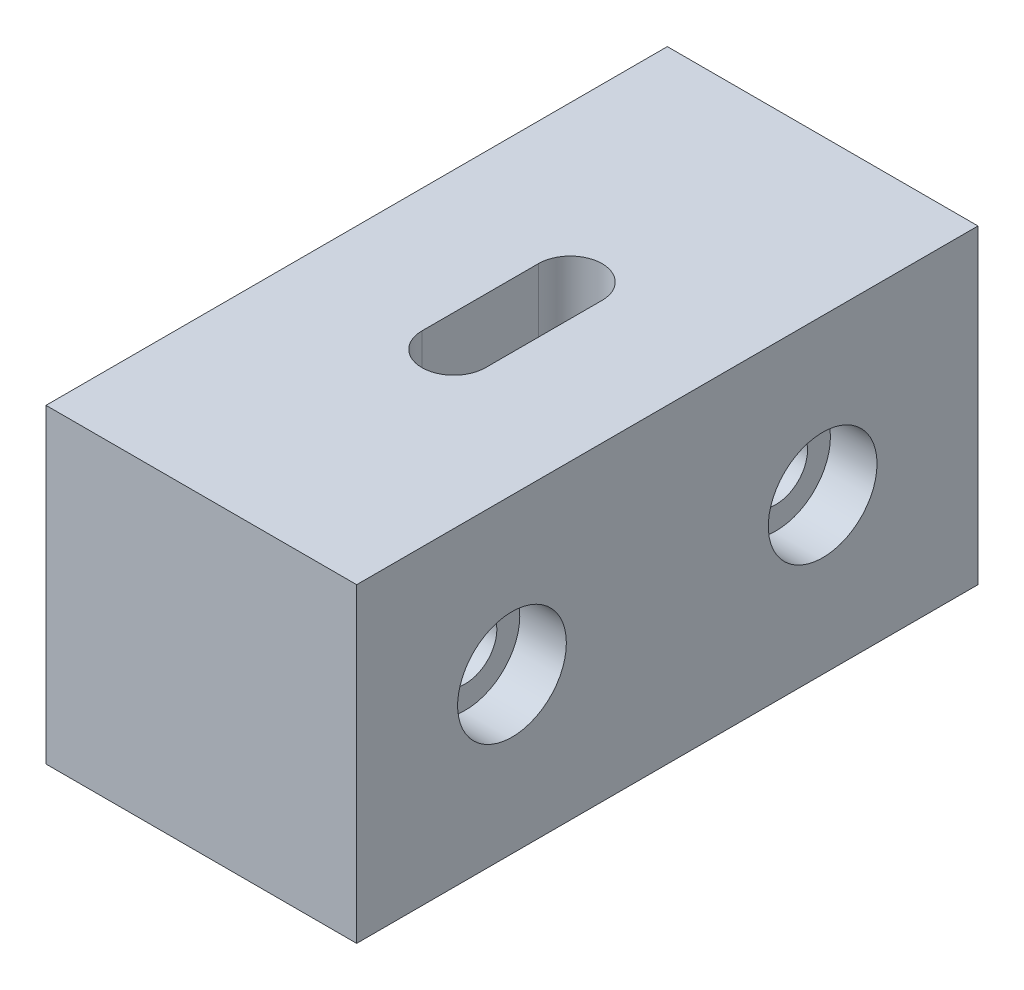
SolidWorks part; units mm, degrees
ref_plane "Front Plane" through (0, 0, 0) normal (0, 0, 1) x (1, 0, 0)
ref_plane "Top Plane" through (0, 0, 0) normal (0, 1, 0) x (1, 0, 0)
ref_plane "Right Plane" through (0, 0, 0) normal (1, 0, 0) x (0, 0, -1)
sketch "Sketch1" plane through (0, 0, 0) normal (0, 0, 1) x (1, 0, 0)
  line L5 (-20, -20) -> (20, -20)
  line L6 (-20, -20) -> (-20, 20)
  line L11 (-20, 20) -> (20, 20)
  line L12 (20, -20) -> (20, 20)
  line L17 (-20, -20) -> (20, 20) construction
  line L18 (-20, 20) -> (20, -20) construction
  point P0 (0, 0)
  dimension "D1" = 40
  dimension "D2" = 40
extrude "Boss-Extrude1" add sketch "Sketch1" along normal blind 40 and the other way blind 40 contours L11 L12 L5 L6 | L5 L12 L11 L6 region at (0, 0, 0)
sketch "Sketch2" plane through (0, 0, 0) normal (1, 0, 0) x (0, 0, -1)
  line L0 (-20, 0) -> (20, 0) construction
  circle A0 centre (-20, 0) radius 4.05
  circle A1 centre (20, 0) radius 4.05
  dimension "D2" = 8.1
  dimension "D1" = 40
extrude "Cut-Extrude1" cut sketch "Sketch2" against normal blind 80 and the other way blind 80
sketch "Sketch3" plane through (0, 0, 0) normal (1, 0, 0) x (0, 0, -1)
  circle A0 centre (-20, 0) radius 7
  circle A1 centre (20, 0) radius 7
  dimension "D1" = 14
extrude "Cut-Extrude2" cut sketch "Sketch3" against normal blind 6 from surface starting at face at (20, 0, 15.95)
sketch "Sketch4" plane through (0, 0, 0) normal (0, 1, 0) x (1, 0, 0)
  line L0 (0, -7.5) -> (0, 7.5) construction
  line L1 (-4.1, -7.5) -> (-4.1, 7.5)
  line L2 (4.1, -7.5) -> (4.1, 7.5)
  arc A0 (-4.1, -7.5) -> (4.1, -7.5) centre (0, -7.5) ccw
  arc A1 (4.1, 7.5) -> (-4.1, 7.5) centre (0, 7.5) ccw
  point P2 (0, 0)
  dimension "D1" = 15
  dimension "D2" = 8.2
extrude "Cut-Extrude3" cut sketch "Sketch4" against normal blind 36 and the other way blind 36
